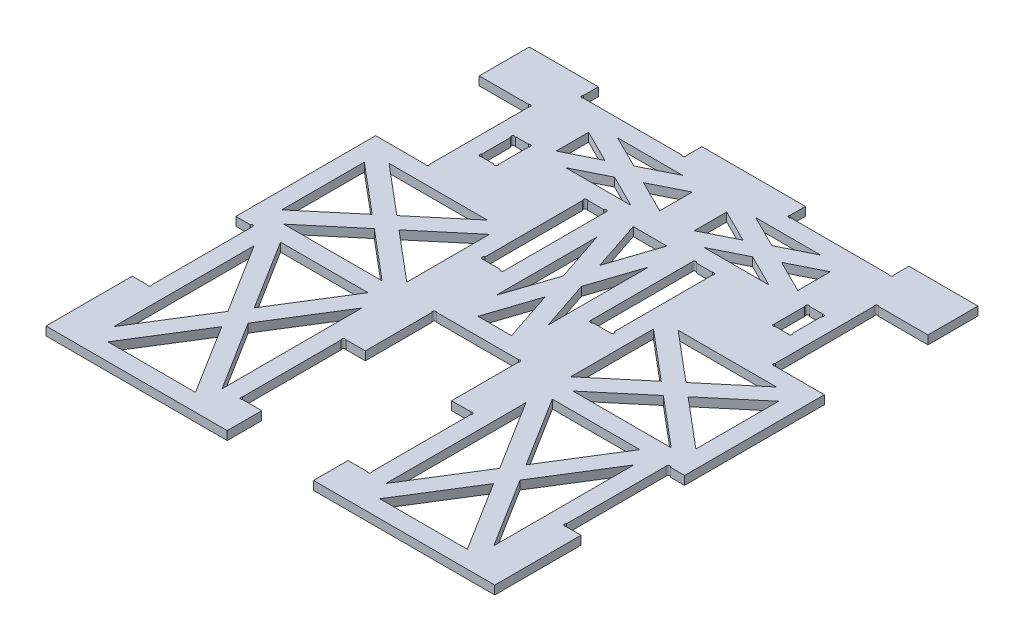
SolidWorks part; units mm, degrees
material "7050-T73510"
ref_plane "Front Plane" through (0, 0, 0) normal (0, 0, 1) x (1, 0, 0)
ref_plane "Top Plane" through (0, 0, 0) normal (0, 1, 0) x (1, 0, 0)
ref_plane "Right Plane" through (0, 0, 0) normal (1, 0, 0) x (0, 0, -1)
sketch "Sketch1" plane through (0, 0, 0) normal (0, 1, 0) x (1, 0, 0)
  line L1 (-165.1, -177.8) -> (165.1, -177.8)
  line L2 (-165.1, -177.8) -> (-165.1, 177.8)
  line L3 (-165.1, 177.8) -> (165.1, 177.8)
  line L4 (165.1, -177.8) -> (165.1, 177.8)
  line L5 (-165.1, -177.8) -> (165.1, 177.8) construction
  line L6 (-165.1, 177.8) -> (165.1, -177.8) construction
  point P0 (0, 0)
  dimension "D1" = 355.6
  dimension "D2" = 330.2
extrude "Boss-Extrude1" add sketch "Sketch1" along normal blind 6.35
sketch "Sketch2" plane through (0, 6.35, 0) normal (0, 1, 0) x (1, 0, 0)
  line L0 (-165.1, -177.8) -> (165.1, -177.8) construction
  line L1 (-31.75, -25.4) -> (31.75, -25.4)
  line L2 (-31.75, -25.4) -> (-31.75, -177.8)
  line L3 (-31.75, -177.8) -> (31.75, -177.8)
  line L4 (31.75, -25.4) -> (31.75, -177.8)
  line L5 (-31.75, -25.4) -> (31.75, -177.8) construction
  line L6 (-31.75, -177.8) -> (31.75, -25.4) construction
  point P0 (0, -101.6)
  dimension "D1" = 152.4
  dimension "D2" = 63.5
extrude "Cut-Extrude1" cut sketch "Sketch2" against normal through all
sketch "Sketch3" plane through (0, 6.35, 0) normal (0, 1, 0) x (1, 0, 0)
  line L0 (165.1, -177.8) -> (165.1, 177.8) construction
  line L5 (152.4, 140.97) -> (127, 140.97)
  line L11 (152.4, 140.97) -> (152.4, 64.77)
  line L13 (152.4, 64.77) -> (127, 64.77)
  line L15 (127, 140.97) -> (127, 64.77)
  line L16 (165.1, 177.8) -> (-165.1, 177.8) construction
  line L17 (114.3, 90.17) -> (101.6, 90.17)
  line L18 (114.3, 90.17) -> (114.3, 115.57)
  line L19 (114.3, 115.57) -> (101.6, 115.57)
  line L20 (101.6, 90.17) -> (101.6, 115.57)
  line L21 (0, -3.4925) -> (0, 3.4925) construction
  line L22 (-101.6, 90.17) -> (-101.6, 115.57)
  line L23 (-114.3, 115.57) -> (-101.6, 115.57)
  line L24 (-114.3, 90.17) -> (-114.3, 115.57)
  line L25 (-114.3, 90.17) -> (-101.6, 90.17)
  line L26 (-127, 140.97) -> (-127, 64.77)
  line L27 (-152.4, 64.77) -> (-127, 64.77)
  line L28 (-152.4, 140.97) -> (-152.4, 64.77)
  line L29 (-152.4, 140.97) -> (-127, 140.97)
  point P14 (114.3, 102.87)
  point P15 (127, 102.87)
  dimension "D1" = 25.4
  dimension "D2" = 12.7
  dimension "D3" = 12.7
  dimension "D4" = 12.7
  dimension "D5" = 25.4
  dimension "D6" = 76.2
  dimension "D7" = 36.83
extrude "Cut-Extrude2" cut sketch "Sketch3" against normal through all contours L5 L15 L13 L11 | L20 L17 L18 L19 | L29 L28 L27 L26 | L24 L25 L22 L23 | L26 L27 L28 L29 region at (139.7, 6.35, -102.87) region at (107.95, 6.35, -102.87) region at (-107.95, 6.35, -102.87) region at (-139.7, 6.35, -102.87)
sketch "Sketch4" plane through (0, 6.35, 0) normal (0, 1, 0) x (1, 0, 0)
  line L0 (-165.1, 177.8) -> (-165.1, -177.8) construction
  line L1 (-165.1, 140.97) -> (-152.4, 140.97)
  line L2 (-165.1, 140.97) -> (-165.1, 64.77)
  line L3 (-165.1, 64.77) -> (-152.4, 64.77)
  line L4 (-152.4, 140.97) -> (-152.4, 64.77)
  line L5 (0, -3.4925) -> (0, 3.4925) construction
  line L6 (-165.1, -114.3) -> (-152.4, -114.3)
  line L7 (-165.1, -114.3) -> (-165.1, -38.1)
  line L8 (-165.1, -38.1) -> (-152.4, -38.1)
  line L9 (-152.4, -114.3) -> (-152.4, -38.1)
  line L10 (165.1, 64.77) -> (152.4, 64.77)
  line L11 (152.4, 140.97) -> (152.4, 64.77)
  line L12 (165.1, 140.97) -> (152.4, 140.97)
  line L13 (165.1, 140.97) -> (165.1, 64.77)
  line L14 (165.1, -38.1) -> (152.4, -38.1)
  line L15 (152.4, -114.3) -> (152.4, -38.1)
  line L16 (165.1, -114.3) -> (152.4, -114.3)
  line L17 (165.1, -114.3) -> (165.1, -38.1)
  line L18 (165.1, 177.8) -> (-165.1, 177.8) construction
  line L19 (114.3, 165.1) -> (38.1, 165.1)
  line L20 (-114.3, 177.8) -> (-38.1, 177.8)
  line L21 (-114.3, 177.8) -> (-114.3, 165.1)
  line L22 (-114.3, 165.1) -> (-38.1, 165.1)
  line L23 (-38.1, 177.8) -> (-38.1, 165.1)
  line L24 (38.1, 177.8) -> (38.1, 165.1)
  line L25 (114.3, 177.8) -> (38.1, 177.8)
  line L26 (114.3, 177.8) -> (114.3, 165.1)
  line L27 (-31.75, -25.4) -> (-31.75, -177.8) construction
  line L28 (-31.75, -152.4) -> (-47.625, -152.4)
  line L29 (-31.75, -152.4) -> (-31.75, -76.2)
  line L30 (-31.75, -76.2) -> (-47.625, -76.2)
  line L31 (-47.625, -152.4) -> (-47.625, -76.2)
  line L32 (-165.1, -177.8) -> (-31.75, -177.8) construction
  line L33 (31.75, 101.6) -> (47.625, 101.6)
  line L34 (-31.75, 25.4) -> (-47.625, 25.4)
  line L35 (-31.75, 25.4) -> (-31.75, 101.6)
  line L36 (-31.75, 101.6) -> (-47.625, 101.6)
  line L37 (-47.625, 25.4) -> (-47.625, 101.6)
  line L38 (47.625, 25.4) -> (47.625, 101.6)
  line L39 (31.75, 25.4) -> (47.625, 25.4)
  line L40 (31.75, 25.4) -> (31.75, 101.6)
  line L41 (31.75, -76.2) -> (47.625, -76.2)
  line L42 (47.625, -152.4) -> (47.625, -76.2)
  line L43 (31.75, -152.4) -> (47.625, -152.4)
  line L44 (31.75, -152.4) -> (31.75, -76.2)
  dimension "D1" = 12.7
  dimension "D2" = 12.7
  dimension "D3" = 76.2
  dimension "D4" = 76.2
  dimension "D5" = 36.83
  dimension "D6" = 215.9
  dimension "D7" = 12.7
  dimension "D8" = 76.2
  dimension "D9" = 76.2
  dimension "D10" = 15.875
  dimension "D11" = 76.2
  dimension "D12" = 25.4
  dimension "D13" = 76.2
  dimension "D14" = 15.875
  dimension "D15" = 203.2
  dimension "D16" = 63.5
extrude "Cut-Extrude3" cut sketch "Sketch4" against normal through all
sketch "Sketch5" plane through (0, 6.35, 0) normal (0, 1, 0) x (1, 0, 0)
  line L0 (-165.1, -177.8) -> (-31.75, -177.8) construction
  line L1 (-139.7, -165.1) -> (-60.325, -165.1)
  line L2 (-139.7, -165.1) -> (-139.7, -38.1)
  line L3 (-139.7, -38.1) -> (-60.325, -38.1)
  line L4 (-60.325, -165.1) -> (-60.325, -38.1)
  line L5 (-139.7, -165.1) -> (-60.325, -38.1) construction
  line L6 (-139.7, -38.1) -> (-60.325, -165.1) construction
  line L7 (-152.4, -25.4) -> (-60.325, -25.4)
  line L8 (-152.4, -25.4) -> (-152.4, 52.07)
  line L9 (-152.4, 52.07) -> (-60.325, 52.07)
  line L10 (-60.325, -25.4) -> (-60.325, 52.07)
  line L11 (-152.4, -25.4) -> (-60.325, 52.07) construction
  line L12 (-152.4, 52.07) -> (-60.325, -25.4) construction
  line L13 (-88.9, 114.3) -> (-12.7, 114.3)
  line L14 (-88.9, 114.3) -> (-88.9, 152.4)
  line L15 (-88.9, 152.4) -> (-12.7, 152.4)
  line L16 (-12.7, 114.3) -> (-12.7, 152.4)
  line L17 (-88.9, 114.3) -> (-12.7, 152.4) construction
  line L18 (-88.9, 152.4) -> (-12.7, 114.3) construction
  line L23 (0, -3.4925) -> (0, 3.4925) construction
  line L24 (-19.05, -12.7) -> (19.05, -12.7)
  line L25 (-152.4, -114.3) -> (-152.4, -38.1) construction
  line L26 (-152.4, -38.1) -> (-165.1, -38.1) construction
  line L27 (-47.625, -76.2) -> (-47.625, -152.4) construction
  line L28 (-165.1, 64.77) -> (-165.1, -38.1) construction
  line L29 (-165.1, 64.77) -> (-127, 64.77) construction
  line L30 (-47.625, 101.6) -> (-47.625, 25.4) construction
  line L31 (-19.05, -12.7) -> (-19.05, 101.6)
  line L32 (-19.05, 101.6) -> (19.05, 101.6)
  line L33 (19.05, -12.7) -> (19.05, 101.6)
  line L34 (-19.05, -12.7) -> (19.05, 101.6) construction
  line L35 (-19.05, 101.6) -> (19.05, -12.7) construction
  line L36 (31.75, -25.4) -> (-31.75, -25.4) construction
  line L37 (-31.75, 25.4) -> (-31.75, 101.6) construction
  line L38 (-31.75, 101.6) -> (-47.625, 101.6) construction
  line L39 (-101.6, 90.17) -> (-101.6, 115.57) construction
  line L40 (-114.3, 165.1) -> (-38.1, 165.1) construction
  line L41 (-145.0848, -41.4655) -> (-65.7098, -168.4655)
  line L42 (-134.3152, -168.4655) -> (-54.9402, -41.4655)
  line L43 (-156.4882, 47.2111) -> (-64.4132, -30.2589)
  line L44 (-148.3118, -30.2589) -> (-56.2368, 47.2111)
  line L45 (-25.0741, 99.592) -> (13.0259, -14.708)
  line L46 (-13.0259, -14.708) -> (25.0741, 99.592)
  line L47 (-91.7398, 146.7204) -> (-15.5398, 108.6204)
  line L48 (-86.0602, 108.6204) -> (-9.8602, 146.7204)
  line L49 (-134.3152, -34.7345) -> (-54.9402, -161.7345)
  line L50 (-145.0848, -161.7345) -> (-65.7098, -34.7345)
  line L51 (-148.3118, 56.9289) -> (-56.2368, -20.5411)
  line L52 (-156.4882, -20.5411) -> (-64.4132, 56.9289)
  line L53 (-13.0259, 103.608) -> (25.0741, -10.692)
  line L54 (-25.0741, -10.692) -> (13.0259, 103.608)
  line L55 (-86.0602, 158.0796) -> (-9.8602, 119.9796)
  line L56 (-91.7398, 119.9796) -> (-15.5398, 158.0796)
  point P0 (-100.0125, -101.6)
  point P5 (-106.3625, 13.335)
  point P10 (-50.8, 133.35)
  point P15 (0, 44.45)
  point P27 (-158.75, -38.1)
  point P45 (-39.6875, 101.6)
  dimension "D1" = 12.7
  dimension "D2" = 12.7
  dimension "D3" = 0
  dimension "D4" = 12.7
  dimension "D5" = 12.7
  dimension "D6" = 12.7
  dimension "D7" = 12.7
  dimension "D8" = 12.7
  dimension "D9" = 12.7
  dimension "D10" = 12.7
  dimension "D11" = 12.7
  dimension "D12" = 12.7
  dimension "D13" = 12.7
  dimension "D14" = 12.7
  dimension "D15" = 6.35
  dimension "D16" = 6.35
extrude "Cut-Extrude4" cut sketch "Sketch5" against normal through all contours L42 L1 L41 | L2 L50 L41 | L49 L50 L3 | L42 L49 L4 | L44 L7 L43 | L8 L52 L43 | L51 L52 L9 | L44 L51 L10 | L46 L53 L33 | L53 L54 L32 | L31 L54 L45 | L46 L24 L45 | L48 L13 L47 | L48 L55 L16 | L55 L56 L15 | L14 L56 L47 region at (-100.0125, 6.35, 147.9271) region at (-128.9669, 6.35, 101.6) region at (-71.0581, 6.35, 101.6) region at (-100.0125, 6.35, 55.2729) region at (-106.3625, 6.35, 15.2545) region at (-140.3419, 6.35, -13.335) region at (-72.3831, 6.35, -13.335) region at (-106.3625, 6.35, -41.9245) region at (-50.8, 6.35, -118.2835) region at (-80.933, 6.35, -133.35) region at (-20.667, 6.35, -133.35) region at (-50.8, 6.35, -148.4165) region at (0, 6.35, 0.3435) region at (-14.9312, 6.35, -44.45) region at (14.9312, 6.35, -44.45) region at (0, 6.35, -89.2435)
mirror "Mirror1" about plane through (0, 0, 0) normal (1, 0, 0) of "Cut-Extrude4"
sketch "Sketch6" plane through (0, 6.35, 0) normal (0, 1, 0) x (1, 0, 0)
  circle A0 centre (-127.8194, 65.7403) radius 1.27
  circle A1 centre (-127.9383, 140.1141) radius 1.27
  circle A2 centre (-113.3907, 165.9867) radius 1.27
  circle A3 centre (-39.124, 165.8512) radius 1.27
  circle A4 centre (-46.8424, 100.5998) radius 1.27
  circle A5 centre (-32.9403, 101.1573) radius 1.27
  circle A7 centre (-47.2982, 26.6272) radius 1.27
  circle A8 centre (-32.9079, 25.9216) radius 1.27
  circle A9 centre (-153.5668, -38.6014) radius 1.27
  circle A10 centre (-153.1517, -113.2764) radius 1.27
  circle A11 centre (-46.7669, -151.4637) radius 1.27
  circle A12 centre (-46.8208, -77.1829) radius 1.27
  circle A13 centre (-30.886, -26.3308) radius 1.27
  circle A14 centre (-113.678, 114.4628) radius 1.27
  circle A15 centre (-102.5148, 114.6891) radius 1.27
  circle A17 centre (-102.6381, 90.9016) radius 1.27
  circle A18 centre (-113.5656, 91.2061) radius 1.27
extrude "Cut-Extrude5" cut sketch "Sketch6" against normal through all
mirror "Mirror2" about plane through (0, 0, 0) normal (1, 0, 0) of "Cut-Extrude5"
